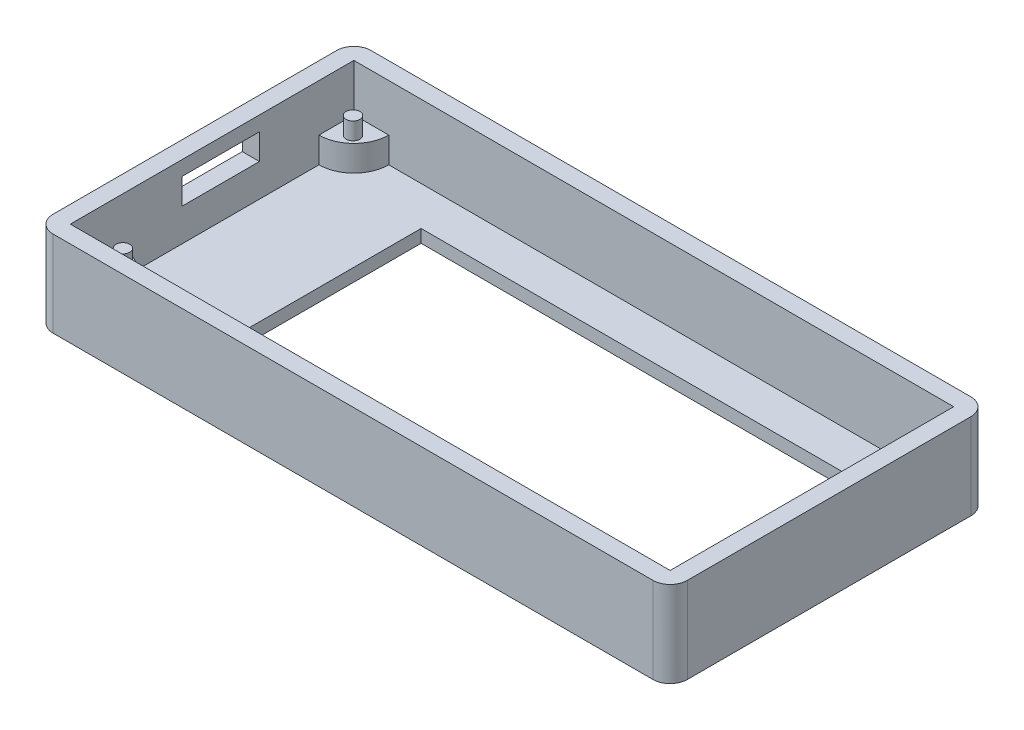
SolidWorks part; units mm, degrees
ref_plane "前视基准面" through (0, 0, 0) normal (0, 0, 1) x (1, 0, 0)
ref_plane "上视基准面" through (0, 0, 0) normal (0, 1, 0) x (1, 0, 0)
ref_plane "右视基准面" through (0, 0, 0) normal (1, 0, 0) x (0, 0, -1)
sketch "草图1" plane through (0, 0, 0) normal (0, 1, 0) x (1, 0, 0)
  line L1 (-34.925, 15.494) -> (34.925, 15.494)
  line L2 (-34.925, 15.494) -> (-34.925, -15.494)
  line L4 (34.925, 15.494) -> (34.925, -15.494)
  line L5 (-34.925, 15.494) -> (34.925, -15.494) construction
  line L6 (-34.925, -15.494) -> (34.925, 15.494) construction
  line L8 (-34.925, -15.494) -> (-34.925, -17.526)
  line L9 (-34.925, -17.526) -> (34.925, -17.526)
  line L10 (34.925, -15.494) -> (34.925, -17.526)
  line L11 (-34.925, -15.494) -> (34.925, -15.494)
  line L12 (-30.861, -17.526) -> (-30.861, 15.494) construction
  line L13 (30.734, 15.494) -> (30.734, -17.526) construction
  line L14 (-22.561, 10.962) -> (-22.561, -13.994)
  line L15 (27.434, 10.962) -> (27.434, -13.994)
  line L16 (0, 15.494) -> (0, -15.494) construction
  line L17 (-34.925, 0) -> (34.925, 0) construction
  line L18 (-22.561, 10.962) -> (27.434, 10.962)
  line L19 (-22.561, -13.994) -> (27.434, -13.994)
  arc A0 (-34.925, -11.43) -> (-31.4055, -17.526) centre (-34.925, -15.494) cw
  arc A1 (-34.925, 11.43) -> (-30.861, 15.494) centre (-34.925, 15.494) ccw
  arc A2 (34.925, 11.43) -> (30.861, 15.494) centre (34.925, 15.494) cw
  arc A3 (34.925, -11.43) -> (31.4055, -17.526) centre (34.925, -15.494) ccw
  point P0 (0, 0)
  dimension "D4" = 4.064
  dimension "D5" = 4.064
  dimension "D1" = 30.988
  dimension "D2" = 69.85
  dimension "D3" = 2.032
  dimension "D7" = 4.191
  dimension "D8" = 8.3
  dimension "D9" = 3.3
  dimension "D10" = 4.532
  dimension "D11" = 3.532
extrude "凸台-拉伸1" add sketch "草图1" along normal blind 1.5 contours L8 L9 L10 L4 L1 L2
extrude "切除-拉伸2" cut sketch "草图1<6>" along normal up to next contours L14 L19 L15 L18
sketch "草图1<6>" plane through (0, 0, 0) normal (0, 1, 0) x (1, 0, 0) same geometry as "草图1"
extrude "拉伸-薄壁1" add sketch "草图1<7>" along normal blind 10 separate body thin contours L4 L10 L9 L8 L2 L1 thin type one direction wall 2
sketch "草图1<7>" plane through (0, 0, 0) normal (0, 1, 0) x (1, 0, 0) same geometry as "草图1"
fillet "圆角1" radius 2 4 edges at (36.925, 5, -17.494) (36.925, 5, 19.526) (-36.925, 5, 19.526) (-36.925, 5, -17.494) first distance on face at (0, 5, -17.494) first distance on face at (0, 5, 19.526)
sketch "草图2" plane through (0, 1.5, 0) normal (0, 1, 0) x (1, 0, 0)
  line L2 (-34.925, -11.43) -> (-34.925, -17.526)
  line L3 (-34.925, -17.526) -> (-31.4055, -17.526)
  line L4 (-30.861, 15.494) -> (-34.925, 15.494)
  line L5 (-34.925, 15.494) -> (-34.925, 11.43)
  line L7 (30.861, 15.494) -> (34.925, 15.494)
  line L8 (34.925, 15.494) -> (34.925, 11.43)
  line L9 (34.925, -11.43) -> (34.925, -17.526)
  line L10 (34.925, -17.526) -> (31.4055, -17.526)
  arc A0 (30.861, 15.494) -> (34.925, 11.43) centre (34.925, 15.494) ccw construction
  arc A1 (34.925, -11.43) -> (31.4055, -17.526) centre (34.925, -15.494) ccw construction
  arc A2 (-31.4055, -17.526) -> (-34.925, -11.43) centre (-34.925, -15.494) ccw construction
  arc A3 (-34.925, 11.43) -> (-30.861, 15.494) centre (-34.925, 15.494) ccw construction
  arc A4 (30.861, 15.494) -> (34.925, 11.43) centre (34.925, 15.494) ccw
  arc A5 (34.925, -11.43) -> (31.4055, -17.526) centre (34.925, -15.494) ccw
  arc A6 (-31.4055, -17.526) -> (-34.925, -11.43) centre (-34.925, -15.494) ccw
  arc A7 (-34.925, 11.43) -> (-30.861, 15.494) centre (-34.925, 15.494) ccw
  line M5 (-34.925, 15.494) -> (-34.925, -17.526)
  line M6 (-34.925, -17.526) -> (34.925, -17.526)
  line M7 (34.925, -17.526) -> (34.925, 15.494)
  line M8 (34.925, 15.494) -> (-34.925, 15.494)
extrude "凸台-拉伸2" add sketch "草图2" along normal blind 3 contours A7 M5 M8 | A6 M6 M5 | A4 M8 M7 | A5 M7 M6 region at (-33.116, 1.5, 14.7977) region at (-33.2002, 1.5, -13.7692) region at (33.116, 1.5, 14.7977) region at (33.2002, 1.5, -13.7692)
sketch "草图3" plane through (0, 4.5, 0) normal (0, 1, 0) x (1, 0, 0)
  line L1 (-32.925, -13.394) -> (-34.925, -13.394) construction
  line L2 (34.925, 11.43) -> (34.925, 15.494) construction
  line L3 (-34.925, -17.526) -> (34.925, -17.526) construction
  line L6 (-34.925, -15.494) -> (34.925, -15.494) construction
  line L8 (-32.925, -13.394) -> (-32.925, -15.494) construction
  line L9 (-34.925, 15.494) -> (-34.925, -15.494) construction
  line L10 (0, 15.494) -> (0, -15.494) construction
  line L11 (-34.925, 0) -> (34.925, 0) construction
  line L12 (0, 15.494) -> (0, -15.494) construction
  line L13 (-34.925, 0) -> (34.925, 0) construction
  circle A2 centre (-32.925, -13.394) radius 0.8
  circle A3 centre (-32.925, 13.394) radius 0.8
  circle A4 centre (32.925, -13.394) radius 0.8
  circle A5 centre (32.925, 13.394) radius 0.8
  dimension "D2" = 0.8
  dimension "D1" = 2
  dimension "D3" = 2.1
extrude "凸台-拉伸3" add sketch "草图3" along normal blind 2
sketch "草图4" plane through (-34.925, 0, 0) normal (1, 0, 0) x (0, 0, -1)
  line L0 (-11.43, 4.5) -> (11.43, 4.5) construction
  line L2 (-4.5, 8.3) -> (4.5, 8.3)
  line L3 (-4.5, 8.3) -> (-4.5, 5.3)
  line L4 (-4.5, 5.3) -> (4.5, 5.3)
  line L5 (4.5, 8.3) -> (4.5, 5.3)
  point P8 (0, 5.3)
  dimension "D1" = 0.8
  dimension "D2" = 3
  dimension "D3" = 9
extrude "切除-拉伸3" cut sketch "草图4" against normal up to next contours L3 L2 L5 L4
